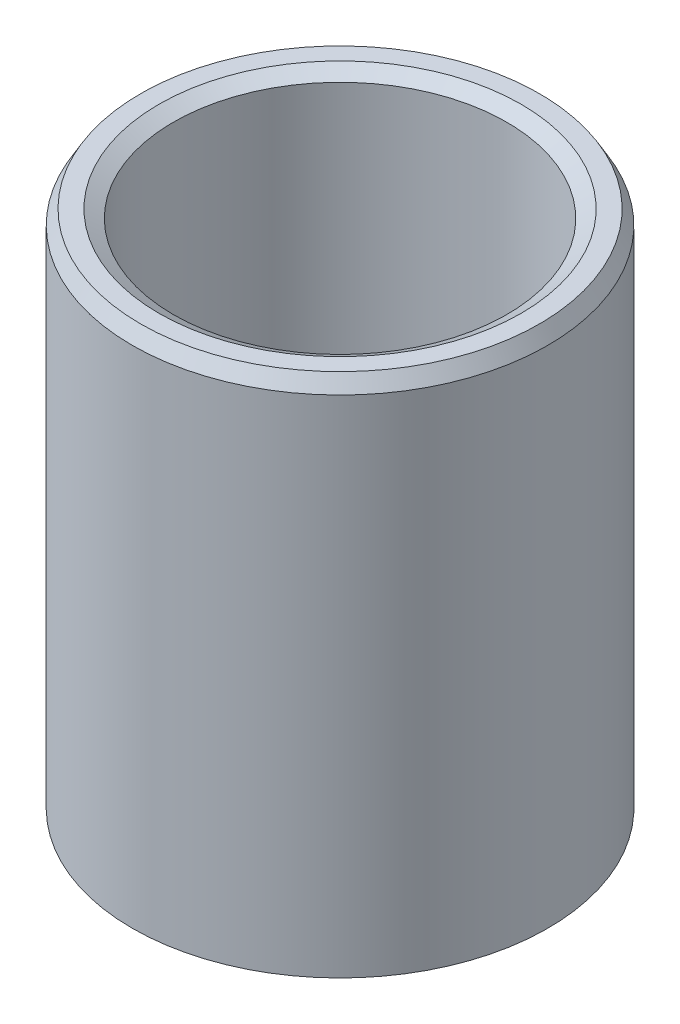
SolidWorks part; units mm, degrees
ref_plane "Front Plane" through (0, 0, 0) normal (0, 0, 1) x (1, 0, 0)
ref_plane "Top Plane" through (0, 0, 0) normal (0, 1, 0) x (1, 0, 0)
ref_plane "Right Plane" through (0, 0, 0) normal (1, 0, 0) x (0, 0, -1)
sketch "Sketch1" plane through (0, 0, 0) normal (0, 1, 0) x (1, 0, 0)
  circle A0 centre (0, 0) radius 32.5
  dimension "SLEEVE_OD" = 65
extrude "Boss-Extrude1" add sketch "Sketch1" along normal blind 82.5203
sketch "Sketch2" plane through (0, 0, 0) normal (0, 1, 0) x (1, 0, 0)
  circle A0 centre (0, 0) radius 26.0756
  dimension "BORE_D" = 52.1513
extrude "Cut-Extrude1" cut sketch "Sketch2" along normal through all
chamfer "Chamfer1" distance 2.2522 angle 30 4 edges at (0, 82.5203, 26.0756) (0, 0, 26.0756) (0, 0, 32.5) (0, 82.5203, 32.5) first distance on face at (0, 82.5203, 26.0756) first distance on face at (0, 0, 26.0756) first distance on face at (0, 82.5203, 32.5)
